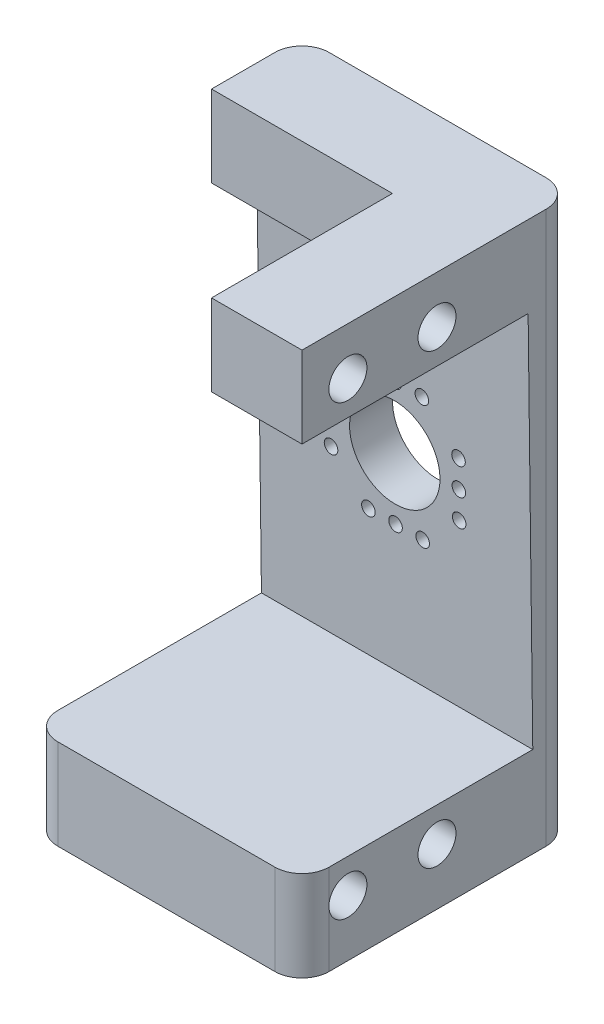
SolidWorks part; units mm, degrees
material "ABS"
ref_plane "前视基准面" through (0, 0, 0) normal (0, 0, 1) x (1, 0, 0)
ref_plane "上视基准面" through (0, 0, 0) normal (0, 1, 0) x (1, 0, 0)
ref_plane "右视基准面" through (0, 0, 0) normal (1, 0, 0) x (0, 0, -1)
other "Configuration Table"
sketch "草图1" plane through (0, 0, 0) normal (0, 0, 1) x (1, 0, 0)
  line L1 (-22.375, 25) -> (22.375, 25)
  line L2 (-22.375, 25) -> (-22.375, -25)
  line L3 (-22.375, -25) -> (22.375, -25)
  line L4 (22.375, 25) -> (22.375, -25)
  line L5 (-22.375, 25) -> (22.375, -25) construction
  line L6 (-22.375, -25) -> (22.375, 25) construction
  point P0 (0, 0)
extrude "凸台-拉伸1" add sketch "草图1" along normal blind 30
shell "抽壳1" thickness 5 removed face at (0, 0, 0) removed face at (0, -25, 15) removed face at (0, 0, 30) outward yes
fillet "圆角1" radius 5 8 edges at (-27.375, 30, 15) (-27.375, 2.5, 30) (-27.375, -25, 15) (-27.375, 2.5, 0) (27.375, -25, 15) (27.375, 2.5, 30) (27.375, 30, 15) (27.375, 2.5, 0)
sketch "草图2" plane through (-27.375, 0, 0) normal (-1, 0, 0) x (0, 0, 1)
  circle A0 centre (15, 7) radius 0.75
  circle A1 centre (12, 7) radius 0.75
  circle A3 centre (18, 7) radius 0.75
  circle A5 centre (8, -3) radius 0.75
  circle A6 centre (8, 0) radius 0.75
  circle A7 centre (8, 3) radius 0.75
  circle A8 centre (12, -7) radius 0.75
  circle A9 centre (15, -7) radius 0.75
  circle A10 centre (18, -7) radius 0.75
  circle A11 centre (22, -3) radius 0.75
  circle A12 centre (22, 0) radius 0.75
  circle A13 centre (22, 3) radius 0.75
extrude "切除-拉伸1" cut sketch "草图2" against normal through all
sketch "草图3" plane through (27.375, 0, 0) normal (1, 0, 0) x (0, 0, -1)
  circle A0 centre (-15, 0) radius 5
extrude "切除-拉伸2" cut sketch "草图3" against normal through all
sketch "草图4" plane through (0, 0, 30) normal (0, 0, 1) x (1, 0, 0)
  line L0 (0, 30) -> (-15, 30)
  line L5 (22.375, 30) -> (-22.375, 30) construction
  line L6 (-15, 30) -> (-15, 150)
  line L7 (-15, 150) -> (15, 150)
  line L8 (15, 150) -> (15, 30)
  line L9 (15, 30) -> (0, 30)
extrude "凸台-拉伸2" add sketch "草图4" against normal blind 30
sketch "草图6" plane through (0, 0, 30) normal (0, 0, 1) x (1, 0, 0)
  line L1 (-15, 150) -> (-15, 30) construction
  line L2 (-15, 99) -> (15, 99)
  line L3 (15, 30) -> (15, 150) construction
  line L5 (15, 150) -> (-15, 150) construction
  line L9 (5, 141) -> (5, 150)
  line L12 (-15, 141) -> (-15, 99)
  line L13 (5, 150) -> (-15, 150)
  line L14 (-15, 150) -> (-15, 141)
  line L15 (5, 141) -> (15, 141)
  line L16 (15, 141) -> (15, 99)
extrude "切除-拉伸3" cut sketch "草图6" against normal blind 20
sketch "草图7" plane through (15, 0, 0) normal (1, 0, 0) x (0, 0, -1)
  circle A0 centre (-24.925, 144.75) radius 2.1
  circle A1 centre (-15.075, 144.75) radius 2.1
  circle A4 centre (-15.075, 95.25) radius 2.1
  circle A5 centre (-24.925, 95.25) radius 2.1
  dimension "D1" = 49.5
  dimension "D2" = 49.5
extrude "切除-拉伸4" cut sketch "草图7" against normal through all
sketch "草图8" plane through (0, 0, 30) normal (0, 0, 1) x (1, 0, 0)
  line L1 (-9, 87) -> (9, 87)
  line L4 (-9, 87) -> (-9, 42)
  line L5 (-9, 42) -> (9, 42)
  line L6 (9, 87) -> (9, 42)
  line L7 (-9, 87) -> (9, 42) construction
  line L8 (-9, 42) -> (9, 87) construction
extrude "切除-拉伸5" cut sketch "草图8" against normal blind 10
sketch "草图9" plane through (0, 0, 0) normal (0, 0, -1) x (-1, 0, 0)
  line L8 (-9, 87.5) -> (9, 87.5)
  line L9 (-9, 87.5) -> (-9, 42.5)
  line L10 (-9, 42.5) -> (9, 42.5)
  line L11 (9, 87.5) -> (9, 42.5)
  line L12 (-9, 87.5) -> (9, 42.5) construction
  line L13 (-9, 42.5) -> (9, 87.5) construction
extrude "切除-拉伸6" cut sketch "草图9" against normal blind 10
fillet "圆角2" radius 3 4 edges at (15, 90, 0) (-15, 90, 0) (-15, 64.5, 30) (15, 64.5, 30)
ref_plane "基准面1" through (0, 89, 0) normal (0, 1, 0) x (1, 0, 0)
sketch "草图10" plane through (0, 89, 0) normal (0, 1, 0) x (1, 0, 0)
  line L1 (-42.7838, 5.8919) -> (42.7838, 5.8919)
  line L2 (-42.7838, 5.8919) -> (-42.7838, -45.2476)
  line L3 (-42.7838, -45.2476) -> (42.7838, -45.2476)
  line L4 (42.7838, 5.8919) -> (42.7838, -45.2476)
  line L5 (-42.7838, 5.8919) -> (42.7838, -45.2476) construction
  line L6 (-42.7838, -45.2476) -> (42.7838, 5.8919) construction
  point P0 (0, -19.6779)
extrude "切除-拉伸7" cut sketch "草图10" against normal through all
sketch "草图11" plane through (15, 0, 0) normal (1, 0, 0) x (0, 0, -1)
  line L0 (-10, 99) -> (-10, 141)
  line L1 (-10, 141) -> (-5, 141)
  line L2 (-5, 141) -> (-4.4849, 99)
  line L3 (-4.4849, 99) -> (-10, 99)
extrude "切除-拉伸8" cut sketch "草图11" against normal through all
sketch "草图12" plane through (0, -0.0401, 3.2703) normal (0, -0.0123, 0.9999) x (1, 0, 0)
  line L0 (-15, 99.3237) -> (-15, 141.112)
  line L1 (-15, 99.0476) -> (-15, 141.0507) construction
  circle A0 centre (-7.0844, 120.1335) radius 0.75
  circle A1 centre (-7.0844, 117.1335) radius 0.75
  circle A2 centre (-7.0844, 123.1335) radius 0.75
  circle A3 centre (3, 113.2178) radius 0.75
  circle A4 centre (0, 113.2178) radius 0.75
  circle A5 centre (-3, 113.2178) radius 0.75
  circle A6 centre (7.0844, 117.1335) radius 0.75
  circle A7 centre (7.0844, 120.1335) radius 0.75
  circle A8 centre (7.0844, 123.1335) radius 0.75
  circle A9 centre (3.0776, 127.015) radius 0.75
  circle A10 centre (0.0778, 127.0487) radius 0.75
  circle A11 centre (-2.922, 127.0824) radius 0.75
  circle A12 centre (0, 120.1335) radius 5
  ellipse E0 centre (-12, 99.3237) end of major axis (-9, 99.3237) minor radius 0.0368 (-12, 99.3604) -> (-15, 99.3237) ccw construction
extrude "切除-拉伸9" cut sketch "草图12" against normal through all contours A12 | A7 | A6 | A9 | A11 | A2 | A1 | A5 | A4 | A3 | A8 | A10 | A0 region at (-7.0844, 117.0846, 4.7067) region at (-7.0844, 123.0841, 4.7803) region at (3, 113.1692, 4.6587) region at (0, 113.1692, 4.6587) region at (-3, 113.1692, 4.6587) region at (7.0844, 117.0846, 4.7067) region at (7.0844, 120.0843, 4.7435) region at (3.0776, 126.9653, 4.8279) region at (-2.922, 127.0328, 4.8287) region at (0, 120.0843, 4.7435)
